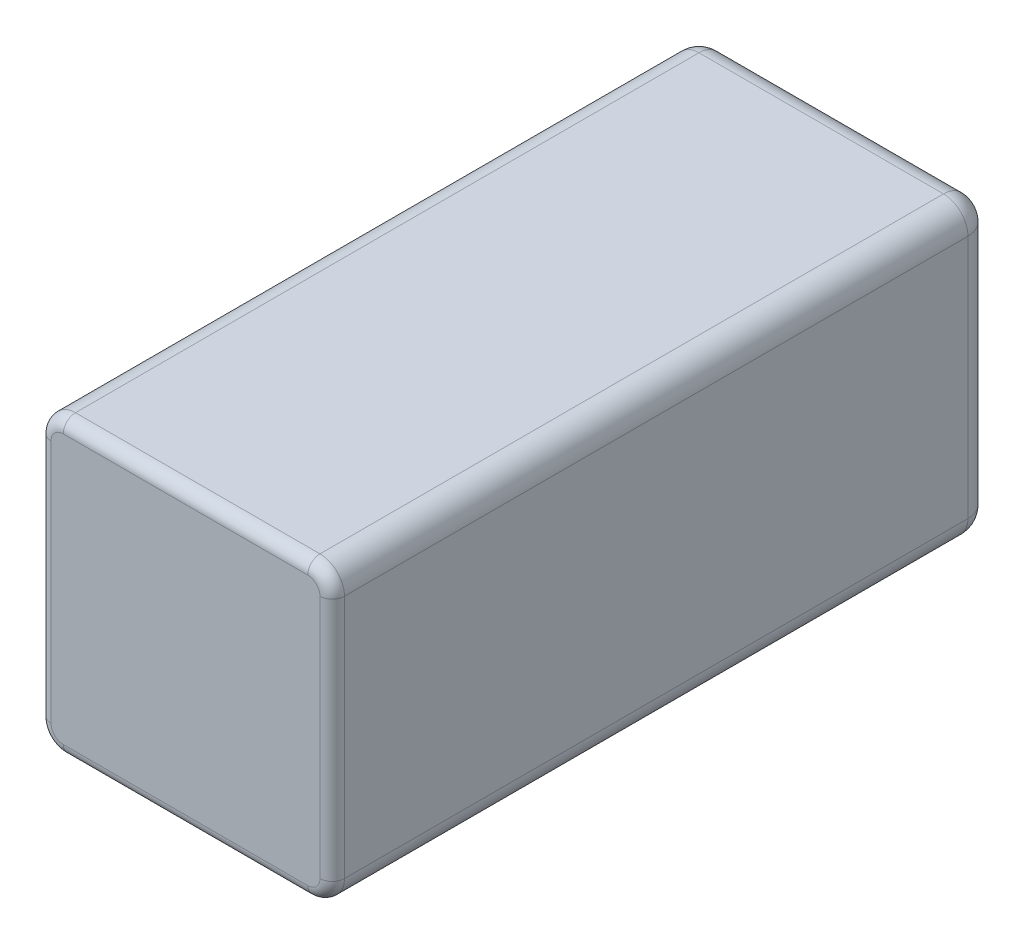
SolidWorks part; units mm, degrees
ref_plane "Front Plane" through (0, 0, 0) normal (0, 0, 1) x (1, 0, 0)
ref_plane "Top Plane" through (0, 0, 0) normal (0, 1, 0) x (1, 0, 0)
ref_plane "Right Plane" through (0, 0, 0) normal (1, 0, 0) x (0, 0, -1)
sketch "Sketch1" plane through (0, 0, 0) normal (0, 0, 1) x (1, 0, 0)
  line L1 (60, 60) -> (-60, 60)
  line L2 (60, 60) -> (60, -60)
  line L3 (60, -60) -> (-60, -60)
  line L4 (-60, 60) -> (-60, -60)
  line L5 (60, 60) -> (-60, -60) construction
  line L6 (60, -60) -> (-60, 60) construction
  point P0 (0, 0)
  dimension "D1" = 120
  dimension "D2" = 120
extrude "Boss-Extrude1" add sketch "Sketch1" along normal blind 220 and the other way blind 50
sketch "Sketch3" plane through (-60, 0, 0) normal (-1, 0, 0) x (0, 0, 1)
  line L1 (20, 10) -> (-20, 10)
  line L2 (20, 10) -> (20, -10)
  line L3 (20, -10) -> (-20, -10)
  line L4 (-20, 10) -> (-20, -10)
  line L5 (20, 10) -> (-20, -10) construction
  line L6 (20, -10) -> (-20, 10) construction
  point P0 (0, 0)
  dimension "D1" = 20
  dimension "D2" = 40
extrude "Cut-Extrude2" cut sketch "Sketch3" against normal blind 10
fillet "Raccordo1" radius 10 4 edges at (60, -60, 85) (-60, -60, 85) (60, 60, 85) (-60, 60, 85)
fillet "Raccordo2" radius 10 8 edges at (57.0711, -57.0711, -50) (-57.0711, -57.0711, -50) (57.0711, 57.0711, -50) (-57.0711, 57.0711, -50) (0, -60, -50) (60, 0, -50) (0, 60, -50) (-60, 0, -50)
fillet "Raccordo3" radius 5 8 edges at (57.0711, -57.0711, 220) (0, -60, 220) (-57.0711, -57.0711, 220) (-57.0711, 57.0711, 220) (57.0711, 57.0711, 220) (60, 0, 220) (0, 60, 220) (-60, 0, 220)
